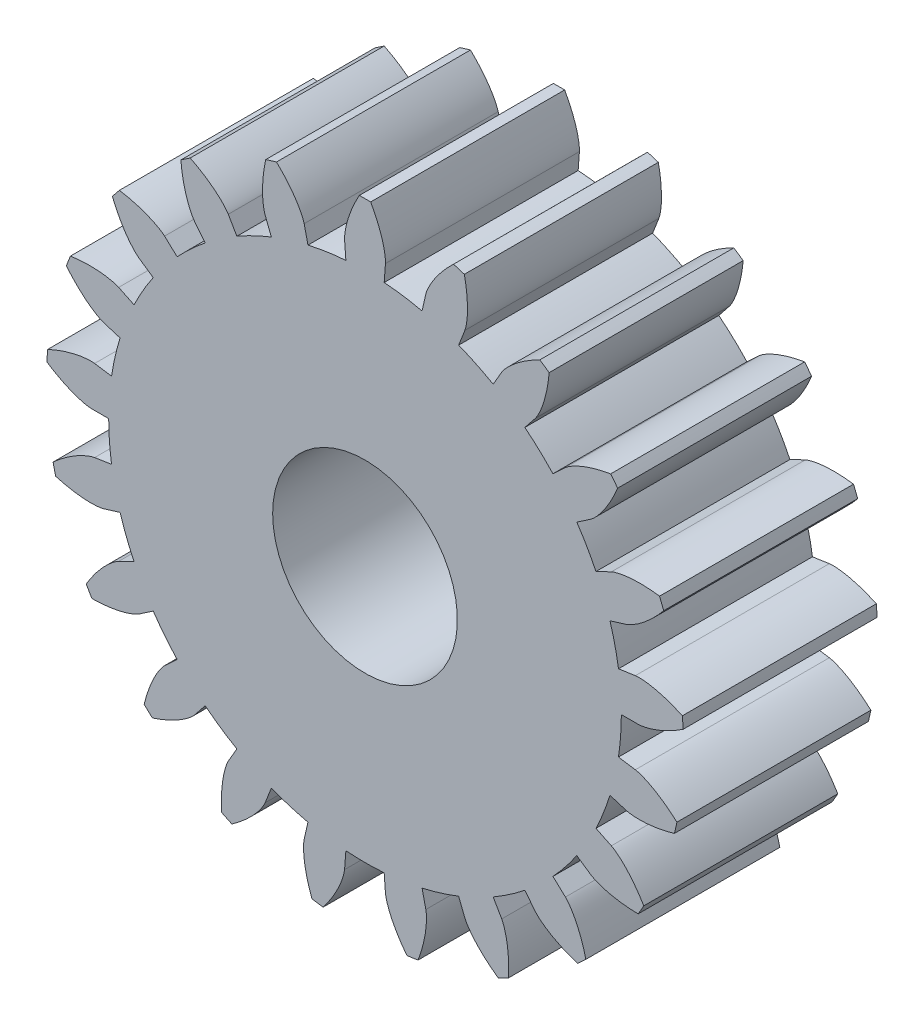
SolidWorks part; units mm, degrees
ref_plane "Přední rovina" through (0, 0, 0) normal (0, 0, 1) x (1, 0, 0)
ref_plane "Vrchní rovina" through (0, 0, 0) normal (0, 1, 0) x (1, 0, 0)
ref_plane "Pravá rovina" through (0, 0, 0) normal (1, 0, 0) x (0, 0, -1)
sketch "Skica1" plane through (0, 0, 0) normal (0, 0, 1) x (1, 0, 0)
  line L0 (0, 0) -> (30097.5517, 0) construction
  line L2 (0, 0) -> (0, 38.5445) construction
  line L3 (2.212, 29.5172) -> (2.0738, 27.6724)
  line L4 (0, 0) -> (2.212, 29.5172) construction
  line L5 (-2.212, 29.5172) -> (-2.0738, 27.6724)
  circle A2 centre (0, 0) radius 31.5 construction
  circle A3 centre (0, 0) radius 34.5
  circle A4 centre (0, 0) radius 27.75
  circle A5 centre (0, 0) radius 10
  circle A6 centre (0, 0) radius 29.6
  spline S0 degree 4 poles (2.212, 29.5172) (2.2126, 29.5251) (2.2139, 29.5471) (2.2153, 29.5889) (2.2157, 29.6572) (2.2137, 29.7444) (2.2081, 29.8571) (2.1978, 29.99) (2.1826, 30.1361) (2.1617, 30.295) (2.1371, 30.4534) (2.1091, 30.6114) (2.078, 30.7687) (2.0366, 30.959) (1.9819, 31.187) (1.9103, 31.4529) (1.8202, 31.7538) (1.719, 32.0596) (1.6116, 32.3597) (1.4942, 32.6619) (1.3743, 32.9535) (1.2407, 33.2551) (1.1128, 33.5329) (0.9594, 33.8425) (0.8328, 34.092) (0.6551, 34.4191) (0.547, 34.6118) (0.4169, 34.8366) (0.3571, 34.9361) (0.3204, 34.9974) knots 0 0 0 0 0 0.005377 0.015084 0.028532 0.04661 0.064855 0.092111 0.119476 0.146842 0.174209 0.201575 0.228941 0.256307 0.307035 0.361767 0.4165 0.471232 0.525964 0.580697 0.635429 0.690161 0.744894 0.799626 0.854358 0.909091 0.954545 1 1 1 1 1 construction
  spline S1 degree 4 poles (2.212, 29.5172) (2.2126, 29.5251) (2.2139, 29.5471) (2.2153, 29.5889) (2.2157, 29.6572) (2.2137, 29.7444) (2.2081, 29.8571) (2.1978, 29.99) (2.1826, 30.1361) (2.1617, 30.295) (2.1371, 30.4534) (2.1091, 30.6114) (2.078, 30.7687) (2.0366, 30.959) (1.9819, 31.187) (1.9103, 31.4529) (1.8202, 31.7538) (1.719, 32.0596) (1.6116, 32.3597) (1.4942, 32.6619) (1.3743, 32.9535) (1.2407, 33.2551) (1.1128, 33.5329) (0.9594, 33.8425) (0.8328, 34.092) (0.6936, 34.3482) (0.6247, 34.4727) (0.5889, 34.5362) knots 0 0 0 0 0 0.005377 0.015084 0.028532 0.04661 0.064855 0.092111 0.119476 0.146842 0.174209 0.201575 0.228941 0.256307 0.307035 0.361767 0.4165 0.471232 0.525964 0.580697 0.635429 0.690161 0.744894 0.799626 0.854358 0.909091 0.909091 0.909091 0.909091 0.909091
  spline S2 degree 4 poles (-2.212, 29.5172) (-2.2126, 29.5251) (-2.2139, 29.5471) (-2.2153, 29.5889) (-2.2157, 29.6572) (-2.2137, 29.7444) (-2.2081, 29.8571) (-2.1978, 29.99) (-2.1826, 30.1361) (-2.1617, 30.295) (-2.1371, 30.4534) (-2.1091, 30.6114) (-2.078, 30.7687) (-2.0366, 30.959) (-1.9819, 31.187) (-1.9103, 31.4529) (-1.8202, 31.7538) (-1.719, 32.0596) (-1.6116, 32.3597) (-1.4942, 32.6619) (-1.3743, 32.9535) (-1.2407, 33.2551) (-1.1128, 33.5329) (-0.9594, 33.8425) (-0.8328, 34.092) (-0.6936, 34.3482) (-0.6247, 34.4727) (-0.5889, 34.5362) knots 0 0 0 0 0 0.005377 0.015084 0.028532 0.04661 0.064855 0.092111 0.119476 0.146842 0.174209 0.201575 0.228941 0.256307 0.307035 0.361767 0.4165 0.471232 0.525964 0.580697 0.635429 0.690161 0.744894 0.799626 0.854358 0.909091 0.909091 0.909091 0.909091 0.909091
  point P8 (-1.9115, 31.4419)
  point P16 (6.2345, 63.7267)
  point P22 (1.9115, 31.4419)
  dimension "D1" = 20
  dimension "D2" = 55.5
  dimension "D3" = 63
  dimension "D4" = 69
  dimension "D5" = 59.2
  dimension "D6" = 4.286
  dimension "D7" = 3.823
extrude "Přidat vysunutím1" add sketch "Skica1" along normal blind 21 contours A4 A5 region at (19.7668, 18.3409, 0)
extrude "Přidat vysunutím2" add sketch "Skica1<3>" along normal blind 21 contours L3 A6 L5 A4 | S2 A6 S1 A3 region at (0, 28.6582, 0) region at (0, 31.6201, 0)
sketch "Skica1<3>" plane through (0, 0, 0) normal (0, 0, 1) x (1, 0, 0) same geometry as "Skica1"
pattern_circular "Kruhové pole1" count 21 over 360 about axis through (0, 0, 21) along (0, 0, 1) of "Přidat vysunutím2"
equation "\"r\"= 50"
